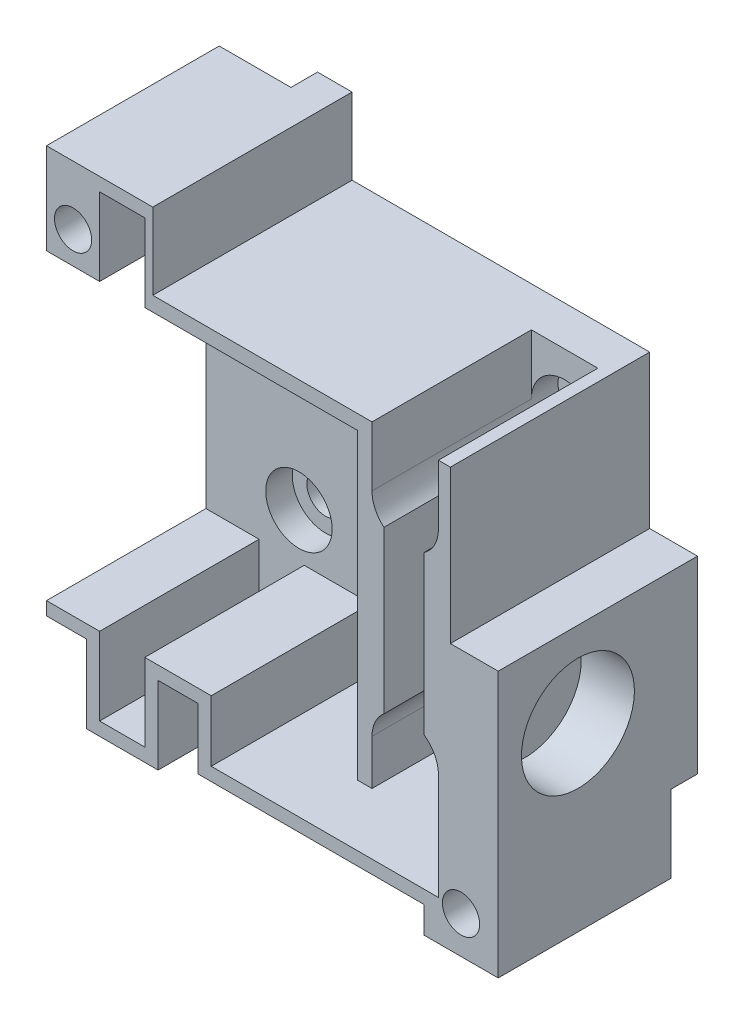
SolidWorks part; units mm, degrees
ref_plane "Front Plane" through (0, 0, 0) normal (0, 0, 1) x (1, 0, 0)
ref_plane "Top Plane" through (0, 0, 0) normal (0, 1, 0) x (1, 0, 0)
ref_plane "Right Plane" through (0, 0, 0) normal (1, 0, 0) x (0, 0, -1)
sketch "Sketch1" plane through (0, 0, 0) normal (0, 0, 1) x (1, 0, 0)
  line L1 (-17, 19) -> (17, 19)
  line L2 (-17, 19) -> (-17, -19)
  line L3 (-17, -19) -> (17, -19)
  line L4 (17, 19) -> (17, -19)
  line L5 (-17, 19) -> (17, -19) construction
  line L6 (-17, -19) -> (17, 19) construction
  point P0 (0, 0)
  dimension "D1" = 38
  dimension "D2" = 34
extrude "Boss-Extrude1" add sketch "Sketch1" along normal blind 16
sketch "Sketch2" plane through (0, 0, 16) normal (0, 0, 1) x (1, 0, 0)
  line L0 (0, 0) -> (-17, 0) construction
  line L5 (-17, 11.4) -> (5.4, 11.4)
  line L6 (-17, 11.4) -> (-17, -11.4)
  line L7 (-17, -11.4) -> (5.4, -11.4)
  line L8 (5.4, 11.4) -> (5.4, -11.4)
  line L9 (-17, 11.4) -> (5.4, -11.4) construction
  line L10 (-17, -11.4) -> (5.4, 11.4) construction
  line L11 (-17, 19) -> (-17, -19) construction
  line L12 (-10.6, -11.4) -> (-10.6, -16.25)
  line L13 (-13, 11.4) -> (-10.6, 11.4)
  line L14 (-13, 11.4) -> (-13, 16.25)
  line L15 (-13, 16.25) -> (-10.6, 16.25)
  line L16 (-10.6, 11.4) -> (-10.6, 16.25)
  line L17 (-13, -11.4) -> (-13, -16.25)
  line L18 (-13, -16.25) -> (-10.6, -16.25)
  line L21 (-17, -11.4) -> (-17, 4.4)
  point P0 (-5.8, 0)
  dimension "D1" = 22.4
  dimension "D2" = 22.8
  dimension "D3" = 5.8
  dimension "D4" = 4
  dimension "D5" = 2.4
  dimension "D6" = 4.85
extrude "Cut-Extrude1" cut sketch "Sketch2" against normal blind 13 contours L8 L5 L6 L7 | L17 L18 L12 L7 | L5 L16 L15 L14
sketch "Sketch3" plane through (0, 0, 16) normal (0, 0, 1) x (1, 0, 0)
  line L1 (5.4, -11.4) -> (-4.6, -11.4)
  line L2 (5.4, -11.4) -> (5.4, -16)
  line L3 (5.4, -16) -> (-4.6, -16)
  line L4 (-4.6, -11.4) -> (-4.6, -16)
  line L5 (5.4, -16) -> (8.4, -16)
  line L6 (5.4, -16) -> (5.4, -11.4)
  line L7 (5.4, -11.4) -> (8.4, -11.4)
  line L8 (8.4, -16) -> (8.4, -11.4)
  line L10 (-17, -19) -> (17, -19) construction
  line L11 (17, 19) -> (-17, 19) construction
  line L12 (8.4, -16) -> (11.4, -16)
  line L13 (8.4, -16) -> (8.4, 19)
  line L14 (8.4, 19) -> (11.4, 19)
  line L15 (11.4, -16) -> (11.4, 19)
  line M11 (17, 19) -> (-17, 19)
  line M21 (5.4, -11.4) -> (-10.6, -11.4)
  dimension "D1" = 3
  dimension "D2" = 10
  dimension "D3" = 3
  dimension "D4" = 3
extrude "Cut-Extrude2" cut sketch "Sketch3" against normal blind 13 contours L12 L15 L13 L8 M11 | L4 L3 L2 M21 | L5 L8 L7 L2 region at (0.4, -13.7, 16) region at (6.9, -13.7, 16) region at (9.9, 1.5, 16)
sketch "Sketch4" plane through (0, 0, 16) normal (0, 0, 1) x (1, 0, 0)
  line L0 (-17, 19) -> (-17, 11.4) construction
  line L3 (-17, -19) -> (17, -19) construction
  line L4 (17, -19) -> (17, 19) construction
  line L5 (8.4, 19) -> (-17, 19) construction
  circle A0 centre (-15, 13.8) radius 1.4
  circle A1 centre (14.2, -16.2) radius 1.4
  dimension "D2" = 5.2
  dimension "D3" = 2.8
  dimension "D4" = 2.8
  dimension "D5" = 2.8
  dimension "D6" = 2.8
  dimension "D1" = 2
extrude "Cut-Extrude3" cut sketch "Sketch4" against normal through all
sketch "Sketch5" plane through (0, 0, 0) normal (0, 0, -1) x (-1, 0, 0)
  line L0 (-17, 19) -> (17, 19) construction
  line L1 (18.4, 13.8) -> (11.6, 13.8)
  line L2 (18.4, 13.8) -> (18.4, 19)
  line L3 (18.4, 19) -> (11.6, 19)
  line L4 (11.6, 13.8) -> (11.6, 19)
  line L5 (-17, -19) -> (-17, 19) construction
  line L6 (-14.2, -19.2) -> (-17, -19.2)
  line L7 (-14.2, -19.2) -> (-14.2, -13.2)
  line L8 (-14.2, -13.2) -> (-17, -13.2)
  line L9 (-17, -19.2) -> (-17, -13.2)
  line L11 (-14.2, -19.2) -> (-10.2, -19.2)
  line L12 (-14.2, -19.2) -> (-14.2, -13.2)
  line L13 (-14.2, -13.2) -> (-10.2, -13.2)
  line L14 (-10.2, -19.2) -> (-10.2, -13.2)
  circle A0 centre (15, 13.8) radius 3.4
  circle A1 centre (-14.2, -16.2) radius 3
  circle M1 centre (15, 13.8) radius 1.4
  circle M2 centre (-14.2, -16.2) radius 1.4
  line M3 (-17, 19) -> (-17, -19)
  line M4 (-17, -19) -> (17, -19)
  line M5 (17, -19) -> (17, 19)
  line M6 (17, 19) -> (-17, 19)
  dimension "D1" = 6.8
  dimension "D2" = 6
  dimension "D3" = 4
extrude "Cut-Extrude5" cut sketch "Sketch5" against normal blind 2 contours A1 L7 M4 M2 | L7 A1 L9 M4 M2 | A1 M3 M4 | A1 L8 M3 | L9 A1 | A1 L7 M4 | A1 L9 L6 M4 | L7 A1 M4 | A0 L2 L3 M5 | A0 L4 M5 M6 | A0 L1 M5 M1 | L1 A0 M5 | A0 L1 M5 | L1 A0 M5 M1 | A1 L14 L13 M4 region at (-17.5712, 12.7332, 0) region at (-17.7757, 17.3011, 0) region at (-17.5712, 14.8668, 0) region at (-14.4405, 12.0641, 0) region at (-14.4405, 15.5359, 0) region at (-13.9912, 17.7377, 0) region at (11.1092, -15.9933, 0) region at (12.7237, -16.1618, 0) region at (13.7943, -19.0802, 0) region at (16.3521, -13.7212, 0) region at (14.6057, -19.0802, 0) region at (15.9461, -19.1069, 0) region at (15.6381, -16.1608, 0) region at (17.0802, -16.2, 0) region at (16.5111, -18.5111, 0)
sketch "Sketch7" plane through (0, 19, 0) normal (0, 1, 0) x (1, 0, 0)
  line L0 (17, -16) -> (17, 0) construction
  line L1 (-17, -16) -> (17, -16)
  line L2 (-17, -16) -> (-17, -15)
  line L3 (-17, -15) -> (17, -15)
  line L4 (17, -16) -> (17, -15)
  dimension "D1" = 1
extrude "Cut-Extrude6" cut sketch "Sketch7" against normal through all
sketch "Sketch9" plane through (0, 0, 15) normal (0, 0, 1) x (1, 0, 0)
  line L0 (8.4, 19) -> (-17, 19) construction
  line L1 (-9, 19) -> (17, 19)
  line L2 (-9, 19) -> (-9, 12.5)
  line L3 (-9, 12.5) -> (17, 12.5)
  line L4 (17, 19) -> (17, 12.5)
  line L5 (17, -19) -> (17, 19) construction
  line L6 (-17, -19) -> (-17, -11.4) construction
  line L7 (-17, -12.4) -> (-14, -12.4)
  line L8 (-17, -12.4) -> (-17, -19)
  line L9 (-17, -19) -> (-14, -19)
  line L10 (-14, -12.4) -> (-14, -19)
  line L11 (17, -19) -> (-17, -19) construction
  line L12 (-13, -16.25) -> (-10.6, -16.25) construction
  line L13 (-8.6, -19) -> (-5.6, -19)
  line L14 (-8.6, -19) -> (-8.6, -12.4)
  line L15 (-8.6, -12.4) -> (-5.6, -12.4)
  line L16 (-5.6, -19) -> (-5.6, -12.4)
  line L17 (-5.6, -19) -> (11.4, -19)
  line L18 (-5.6, -19) -> (-5.6, -17)
  line L19 (-5.6, -17) -> (11.4, -17)
  line L20 (11.4, -19) -> (11.4, -17)
  line L21 (-14, -19) -> (-8.6, -19)
  line L22 (-14, -19) -> (-14, -18.25)
  line L23 (-10.6, -11.4) -> (-4.6, -11.4) construction
  line L24 (-17, -11.4) -> (-13, -11.4) construction
  line L25 (-10.6, -11.4) -> (-10.6, -16.25) construction
  line L26 (-4.6, -11.4) -> (-4.6, -16) construction
  line L27 (-4.6, -16) -> (11.4, -16) construction
  line L28 (-13, -11.4) -> (-13, -16.25) construction
  line L29 (-14, -18.25) -> (-8.6, -18.25)
  line L30 (-8.6, -19) -> (-8.6, -18.25)
  line L32 (-13, 16.25) -> (-10.6, 16.25) construction
  line L33 (-17, 19) -> (-9, 19)
  line L34 (-17, 19) -> (-17, 18.25)
  line L35 (-17, 18.25) -> (-9, 18.25)
  line L36 (-9, 19) -> (-9, 18.25)
  line L37 (11.4, -16) -> (11.4, 19) construction
  line L38 (17, 19) -> (13.4, 19)
  line L39 (17, 19) -> (17, 1)
  line L40 (17, 1) -> (13.4, 1)
  line L41 (13.4, 19) -> (13.4, 1)
  line M21 (8.4, -11.4) -> (8.4, 19)
  line M22 (8.4, 19) -> (-17, 19)
  line M23 (-17, 19) -> (-17, 11.4)
  dimension "D1" = 6.5
  dimension "D2" = 26
  dimension "D3" = 1
  dimension "D4" = 1
  dimension "D5" = 2
  dimension "D6" = 1
  dimension "D7" = 1
  dimension "D8" = 1
  dimension "D9" = 2
  dimension "D10" = 2
  dimension "D11" = 2
  dimension "D12" = 17
  dimension "D13" = 18
extrude "Cut-Extrude9" cut sketch "Sketch9" against normal through all contours L2 L3 M21 M22 | L35 L2 M23 M22 | L41 L1 L3 M21 | L1 L41 L3 L4 | L3 L41 L40 L39 | L17 L20 L19 L16 | L13 L16 L15 L14 | L29 L10 L21 L14 | L10 L7 L8 L9 region at (-0.3, 15.75, 15) region at (-13, 18.625, 15) region at (10.9, 15.75, 15) region at (15.2, 15.75, 15) region at (15.2, 6.75, 15) region at (-15.5, -15.7, 15) region at (-11.3, -18.625, 15) region at (-7.1, -15.7, 15) region at (2.9, -18, 15)
sketch "Sketch10" plane through (0, 0, 3) normal (0, 0, 1) x (1, 0, 0)
  line L1 (-10, 8) -> (10, 8)
  line L2 (-10, 8) -> (-10, -8)
  line L3 (-10, -8) -> (10, -8)
  line L4 (10, 8) -> (10, -8)
  line L5 (-10, 8) -> (10, -8) construction
  line L6 (-10, -8) -> (10, 8) construction
  circle A0 centre (-10, 8) radius 2.5
  circle A1 centre (10, 8) radius 2.5
  circle A2 centre (-10, -8) radius 2.5
  circle A3 centre (10, -8) radius 2.5
  point P0 (0, 0)
  line M6 (8.4, 12.5) -> (8.4, -11.4)
  line M22 (11.4, -16) -> (11.4, 12.5)
  dimension "D3" = 5
  dimension "D1" = 20
  dimension "D2" = 16
extrude "Cut-Extrude10" cut sketch "Sketch10" against normal blind 2 and the other way through all contours L2 A0 L1 | L1 A0 L2 | A1 L4 L1 M6 | A1 L1 L4 M22 M6 | A1 M22 | A1 L1 M6 | L1 A1 M6 | L3 A2 L2 | L2 A2 L3 | A3 L4 L3 M22 M6 | A3 M22 | L4 A3 L3 M6 | A3 L3 M6 | L3 A3 M6 region at (-10.3537, 8.3537, 3) region at (-8.939, 6.939, 3) region at (8.0338, 8.7415, 3) region at (8.0338, 7.2585, 3) region at (-8.939, -6.939, 3) region at (-10.3537, -8.3537, 3) region at (10.1596, 8.4183, 3) region at (9.2324, 6.8354, 3) region at (11.8495, 8, 3) region at (8.0338, -7.2585, 3) region at (9.2324, -6.8354, 3) region at (8.0338, -8.7415, 3) region at (10.1596, -8.4183, 3) region at (11.8495, -8, 3)
sketch "Sketch11" plane through (0, 0, 15) normal (0, 0, 1) x (1, 0, 0)
  line L5 (5.4, -11.4) -> (8.4, -11.4) construction
  line L6 (12.5, -8) -> (7.5, -8)
  line L7 (12.5, -8) -> (12.5, -11.4)
  line L8 (11.4, -11.4) -> (7.5, -11.4)
  line L9 (7.5, -8) -> (7.5, -11.4)
  line L10 (-9, 12.5) -> (8.4, 12.5) construction
  line L11 (12.5, 8) -> (7.5, 8)
  line L12 (12.5, 8) -> (12.5, 12.5)
  line L13 (12.5, 12.5) -> (7.5, 12.5)
  line L14 (7.5, 8) -> (7.5, 12.5)
  line L16 (11.4, -16) -> (12.5, -16)
  line L17 (11.4, -16) -> (11.4, -11.4)
  line L19 (12.5, -16) -> (12.5, -11.4)
  arc A0 (11.4, -10.0712) -> (11.4, -5.9288) centre (10, -8) ccw construction
  arc A1 (11.4, 5.9288) -> (11.4, 10.0712) centre (10, 8) ccw construction
extrude "Cut-Extrude11" cut sketch "Sketch11" against normal blind 12
sketch "Sketch12" plane through (0, 0, 15) normal (0, 0, 1) x (1, 0, 0)
  line L1 (-10.6, 11.4) -> (-9.6, 11.4)
  line L2 (-10.6, 11.4) -> (-10.6, 16.25)
  line L3 (-10.6, 16.25) -> (-9.6, 16.25)
  line L4 (-9.6, 11.4) -> (-9.6, 16.25)
  line L5 (-10.6, -11.4) -> (-9.6, -11.4)
  line L6 (-10.6, -11.4) -> (-10.6, -16.25)
  line L7 (-10.6, -16.25) -> (-9.6, -16.25)
  line L8 (-9.6, -11.4) -> (-9.6, -16.25)
  line L10 (5.4, -11.4) -> (6.4, -11.4)
  line L11 (5.4, -11.4) -> (5.4, 11.4)
  line L12 (5.4, 11.4) -> (6.4, 11.4)
  line L13 (6.4, -11.4) -> (6.4, 11.4)
  dimension "D1" = 1
  dimension "D2" = 1
  dimension "D3" = 4.85
  dimension "D4" = 4.85
  dimension "D5" = 1
extrude "Cut-Extrude12" cut sketch "Sketch12" against normal blind 12
sketch "Sketch14" plane through (17, 0, 0) normal (1, 0, 0) x (0, 0, -1)
  line L0 (-15, -19) -> (-15, 1) construction
  line L1 (-15, -19) -> (-2, -19) construction
  circle A0 centre (-9, -5.4) radius 4.25
  dimension "D1" = 8.5
  dimension "D2" = 6
  dimension "D3" = 13.6
extrude "Cut-Extrude13" cut sketch "Sketch14" against normal blind 4
sketch "Sketch17" plane through (0, 0, 15) normal (0, 0, 1) x (1, 0, 0)
  line L1 (-13, 16.25) -> (-9.6, 16.25)
  line L2 (-13, 16.25) -> (-13, 17.25)
  line L3 (-13, 17.25) -> (-9.6, 17.25)
  line L4 (-9.6, 16.25) -> (-9.6, 17.25)
  line L7 (-9.6, -16.25) -> (-13, -16.25)
  line L8 (-9.6, -16.25) -> (-9.6, -17.25)
  line L9 (-9.6, -17.25) -> (-13, -17.25)
  line L10 (-13, -16.25) -> (-13, -17.25)
  dimension "D1" = 1
  dimension "D2" = 3.4
  dimension "D3" = 1
  dimension "D4" = 3.4
extrude "Cut-Extrude16" cut sketch "Sketch17" against normal blind 12
sketch "Sketch18" plane through (0, 0, 1) normal (0, 0, 1) x (1, 0, 0)
  circle A1 centre (-10, 8) radius 1.4
  circle A2 centre (10, 8) radius 1.4
  circle A3 centre (-10, -8) radius 1.4
  circle A4 centre (10, -8) radius 1.4
  dimension "D1" = 2.8
  dimension "D2" = 2.8
  dimension "D3" = 2.8
  dimension "D4" = 2.8
extrude "Cut-Extrude17" cut sketch "Sketch18" against normal blind 12
